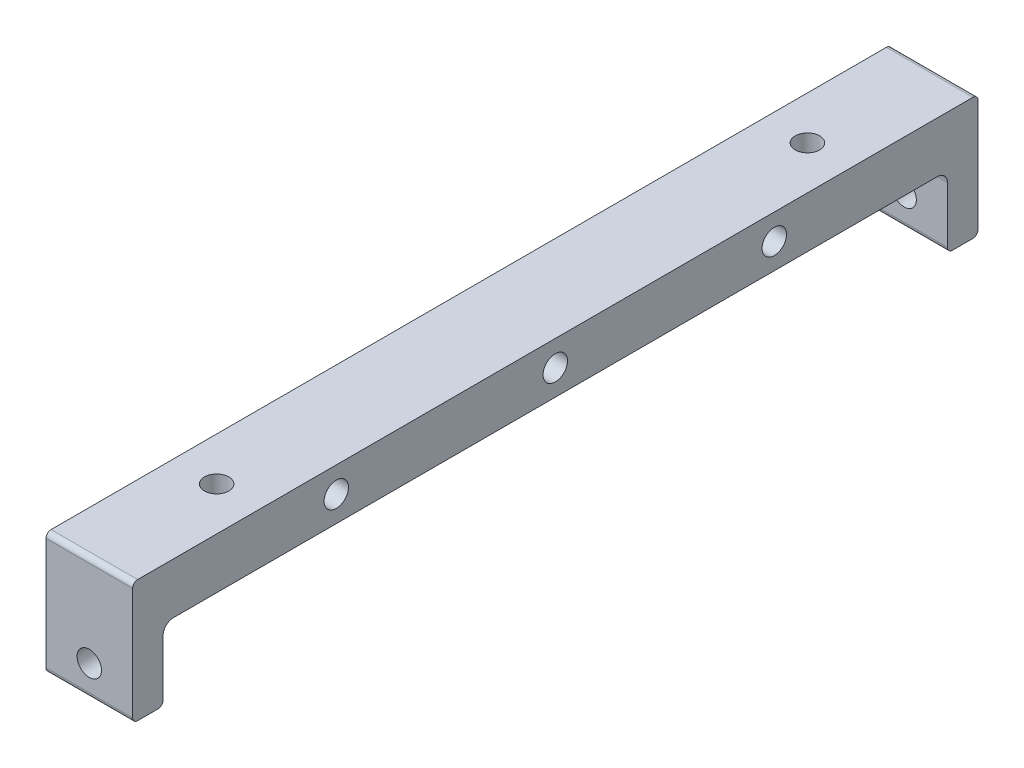
SolidWorks part; units mm, degrees
material "6061 Alloy"
ref_plane "Frontal" through (0, 0, 0) normal (0, 0, 1) x (1, 0, 0)
ref_plane "Superior" through (0, 0, 0) normal (0, 1, 0) x (1, 0, 0)
ref_plane "Direito" through (0, 0, 0) normal (1, 0, 0) x (0, 0, -1)
sketch "Sketch1" plane through (0, 0, 0) normal (0, 0, 1) x (1, 0, 0)
  line L1 (-4.25, -6) -> (4.25, -6)
  line L2 (-4.25, -6) -> (-4.25, 6)
  line L3 (-4.25, 6) -> (4.25, 6)
  line L4 (4.25, -6) -> (4.25, 6)
  line L5 (-4.25, -6) -> (4.25, 6) construction
  line L6 (-4.25, 6) -> (4.25, -6) construction
  point P0 (0, 0)
  dimension "D1" = 8.5
  dimension "D2" = 12
extrude "Boss-Extrude1" add sketch "Sketch1" along normal mid plane 83
sketch "Sketch2" plane through (4.25, 0, 0) normal (1, 0, 0) x (0, 0, -1)
  line L0 (-37.5, 1) -> (37.5, 1)
  line L1 (38.5, 0) -> (38.5, -6)
  line L2 (-41.5, -6) -> (41.5, -6) construction
  line L3 (38.5, -6) -> (-38.5, -6)
  line L4 (-38.5, -6) -> (-38.5, 0)
  line L5 (-41.5, 6) -> (41.5, 6) construction
  line L6 (-41.5, -6) -> (-41.5, 6) construction
  line L7 (41.5, -6) -> (41.5, 6) construction
  arc A0 (37.5, 1) -> (38.5, 0) centre (37.5, 0) cw
  arc A1 (-37.5, 1) -> (-38.5, 0) centre (-37.5, 0) ccw
  dimension "D4" = 1
  dimension "D5" = 1
  dimension "D1" = 5
  dimension "D2" = 3
  dimension "D3" = 3
extrude "Cut-Extrude1" cut sketch "Sketch2" against normal through all
fillet "Fillet1" radius 0.5 6 edges at (0, -6, 38.5) (0, -6, 41.5) (0, -6, -38.5) (0, -6, -41.5) (0, 6, 41.5) (0, 6, -41.5)
hole_wizard "M2 Hole1 - R" positions "Sketch6" profile "Sketch5" countersink size "M2" standard "DIN" end condition through all
sketch "Sketch6" plane through (-4.25, 0, 0) normal (-1, 0, 0) x (0, 0, 1)
  line L0 (41, 6) -> (-41, 6) construction
  line L1 (-41.5, 5.5) -> (-41.5, -5.5) construction
  line L2 (41.5, -5.5) -> (41.5, 5.5) construction
  point P0 (-21.5, 3.5)
  point P2 (21.5, 3.5)
  point P10 (41.5, 0)
  dimension "D1" = 2.5
  dimension "D2" = 20
  dimension "D3" = 20
sketch "Sketch5" plane through (-4.25, 3.5, -21.5) normal (0, 1, 0) x (0, 0, 1)
  line L0 (0, 0) -> (0, 8.5)
  line L1 (0, 8.5) -> (1.2, 8.5)
  line L2 (1.2, 8.5) -> (1.2, 1)
  line L3 (1.2, 1) -> (2.2, 0)
  line L5 (2.2, 0) -> (0, 0)
  line L6 (-1.2, 1) -> (-2.2, 0) construction
  line L11 (0, -6.35) -> (0, 107.95) construction
  dimension "Thru Hole Dia." = 2.4
  dimension "Thru Hole Depth" = 8.5
  dimension "Near C'Sink Dia." = 4.4
  dimension "Near C'Sink Angle" = 90
hole_wizard "M2 Hole2 - T" positions "Sketch13" profile "Sketch12" hole size "M2" standard "DIN"
sketch "Sketch13" plane through (4.25, 0, 0) normal (1, 0, 0) x (0, 0, -1)
  line L0 (-41, 6) -> (41, 6) construction
  point P0 (0, 3.5)
  dimension "D1" = 2.5
sketch "Sketch12" plane through (4.25, 3.5, 0) normal (0, 1, 0) x (0, 0, -1)
  line L0 (0, 0) -> (0, 4.721)
  line L1 (0, 4.721) -> (1.2, 4)
  line L2 (1.2, 4) -> (1.2, 0)
  line L5 (1.2, 0) -> (0, 0)
  line L10 (0, 4.721) -> (-1.2, 4) construction
  line L11 (0, -6.35) -> (0, 107.95) construction
  dimension "Hole Dia." = 2.4
  dimension "Hole Depth" = 4
  dimension "Drill Angle" = 118
hole_wizard "M2 Hole3 - U" positions "Sketch8" profile "Sketch7" hole size "M2" standard "DIN"
sketch "Sketch8" plane through (0, 0, 41.5) normal (0, 0, 1) x (1, 0, 0)
  line L0 (4.25, -6) -> (-4.25, -6) construction
  point P0 (0, -3)
  dimension "D1" = 3
sketch "Sketch7" plane through (0, -3, 41.5) normal (1, 0, 0) x (0, -1, 0)
  line L0 (0, 0) -> (0, 10.721)
  line L1 (0, 10.721) -> (1.2, 10)
  line L2 (1.2, 10) -> (1.2, 0)
  line L5 (1.2, 0) -> (0, 0)
  line L10 (0, 10.721) -> (-1.2, 10) construction
  line L11 (0, -6.35) -> (0, 107.95) construction
  dimension "Hole Dia." = 2.4
  dimension "Hole Depth" = 10
  dimension "Drill Angle" = 118
hole_wizard "M2 Hole4 - V" positions "Sketch15" profile "Sketch14" hole size "M2" standard "DIN" end condition through all
sketch "Sketch15" plane through (0, 6, 0) normal (0, 1, 0) x (1, 0, 0)
  line L0 (4.25, -41) -> (4.25, 41) construction
  line L1 (-4.25, 41.5) -> (4.25, 41.5) construction
  line L2 (4.25, -41.5) -> (-4.25, -41.5) construction
  point P0 (0, 29)
  point P2 (0, -29)
  dimension "D1" = 4.25
  dimension "D2" = 12.5
  dimension "D3" = 12.5
sketch "Sketch14" plane through (0, 6, -29) normal (1, 0, 0) x (0, 0, 1)
  line L0 (0, 0) -> (0, 12)
  line L1 (0, 12) -> (1.2, 12)
  line L2 (1.2, 12) -> (1.2, 0)
  line L5 (1.2, 0) -> (0, 0)
  line L11 (0, -6.35) -> (0, 107.95) construction
  dimension "Thru Hole Dia." = 2.4
  dimension "Thru Hole Depth" = 12
hole_wizard "M2 Hole5 - W" positions "Sketch10" profile "Sketch9" hole size "M2" standard "DIN"
sketch "Sketch10" plane through (-4.25, 0, 0) normal (-1, 0, 0) x (0, 0, 1)
  line L0 (41, 6) -> (-41, 6) construction
  line L1 (41.5, 5.5) -> (41.5, -5.5) construction
  line L2 (-41.5, 5.5) -> (-41.5, -5.5) construction
  point P0 (-35.5, 3.5)
  point P2 (35.5, 3.5)
  dimension "D1" = 2.5
  dimension "D2" = 6
  dimension "D3" = 6
sketch "Sketch9" plane through (-4.25, 3.5, -35.5) normal (0, 1, 0) x (0, 0, 1)
  line L0 (0, 0) -> (0, 5.721)
  line L1 (0, 5.721) -> (1.2, 5)
  line L2 (1.2, 5) -> (1.2, 0)
  line L5 (1.2, 0) -> (0, 0)
  line L10 (0, 5.721) -> (-1.2, 5) construction
  line L11 (0, -6.35) -> (0, 107.95) construction
  dimension "Hole Dia." = 2.4
  dimension "Hole Depth" = 5
  dimension "Drill Angle" = 118
hole_wizard "M2 Hole6 - Y" positions "Sketch17" profile "Sketch16" hole size "M2" standard "DIN"
sketch "Sketch17" plane through (0, 0, -41.5) normal (0, 0, -1) x (-1, 0, 0)
  line L0 (4.25, 5.5) -> (4.25, -5.5) construction
  line L1 (-4.25, 6) -> (4.25, 6) construction
  point P0 (0, -3)
  dimension "D1" = 4.25
  dimension "D2" = 9
sketch "Sketch16" plane through (0, -3, -41.5) normal (1, 0, 0) x (0, 1, 0)
  line L0 (0, 0) -> (0, 10.721)
  line L1 (0, 10.721) -> (1.2, 10)
  line L2 (1.2, 10) -> (1.2, 0)
  line L5 (1.2, 0) -> (0, 0)
  line L10 (0, 10.721) -> (-1.2, 10) construction
  line L11 (0, -6.35) -> (0, 107.95) construction
  dimension "Hole Dia." = 2.4
  dimension "Hole Depth" = 10
  dimension "Drill Angle" = 118
